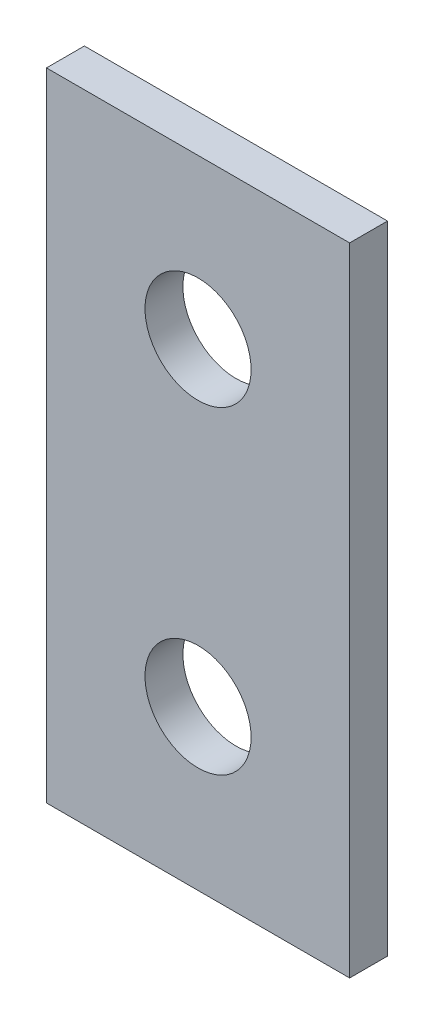
SolidWorks part; units mm, degrees
ref_plane "Alzado" through (0, 0, 0) normal (0, 0, 1) x (1, 0, 0)
ref_plane "Planta" through (0, 0, 0) normal (0, 1, 0) x (1, 0, 0)
ref_plane "Vista lateral" through (0, 0, 0) normal (1, 0, 0) x (0, 0, -1)
sketch "Croquis4" plane through (0, 0, 0) normal (0, 0, 1) x (1, 0, 0)
  line L0 (0, 0) -> (0, 84)
  line L1 (0, 84) -> (40, 84)
  line L2 (40, 84) -> (40, 0)
  line L3 (40, 0) -> (0, 0)
  dimension "D1" = 84
  dimension "D2" = 40
extrude "Saliente-Extruir3" add sketch "Croquis4" along normal blind 5
sketch "Croquis5" plane through (0, 0, 5) normal (0, 0, 1) x (1, 0, 0)
  line L0 (20, 0) -> (20, 21) construction
  line L1 (0, 0) -> (40, 0) construction
  circle A0 centre (20, 21) radius 7
  circle A1 centre (20, 63) radius 7
  dimension "D1" = 21
  dimension "D2" = 42
extrude "Cortar-Extruir1" cut sketch "Croquis5" against normal blind 5 contours A1
extrude "Cortar-Extruir2" cut sketch "Croquis5<3>" against normal blind 5 contours A0
sketch "Croquis5<3>" plane through (0, 0, 5) normal (0, 0, 1) x (1, 0, 0) same geometry as "Croquis5"
